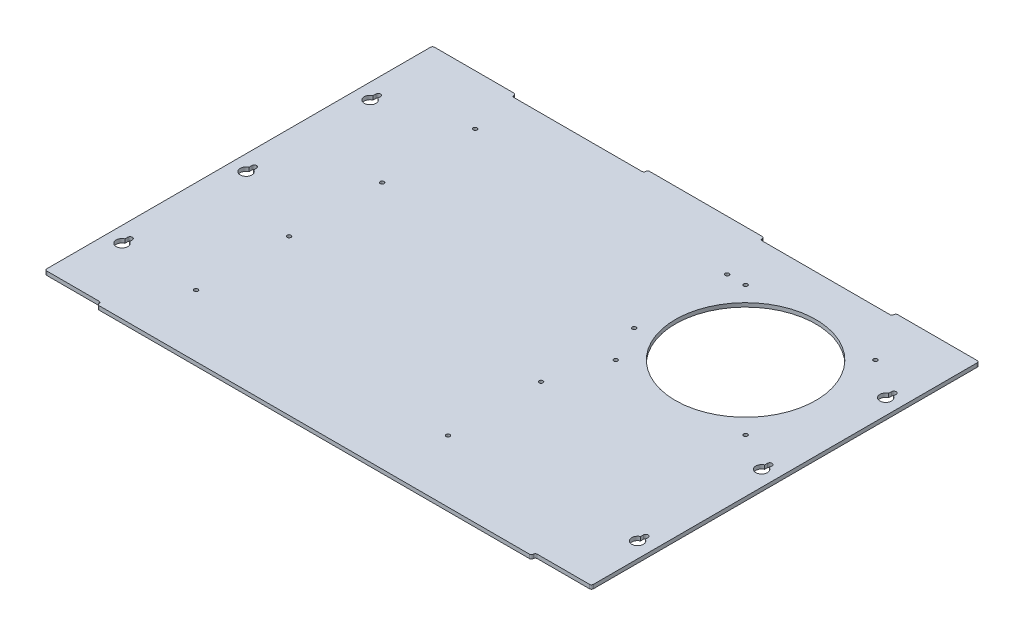
SolidWorks part; units mm, degrees
ref_plane "Front Plane" through (0, 0, 0) normal (0, 0, 1) x (1, 0, 0)
ref_plane "Top Plane" through (0, 0, 0) normal (0, 1, 0) x (1, 0, 0)
ref_plane "Right Plane" through (0, 0, 0) normal (1, 0, 0) x (0, 0, -1)
sketch "Sketch1" plane through (0, 0, 0) normal (0, 1, 0) x (1, 0, 0)
  line L0 (401.6375, 0) -> (447.675, 0)
  line L1 (0, 0) -> (46.0375, 0)
  line L2 (0, 0) -> (0, 317.5)
  line L3 (0, 317.5) -> (447.675, 317.5)
  line L4 (447.675, 0) -> (447.675, 317.5)
  line L6 (46.0375, 0) -> (46.0375, -3.175)
  line L7 (46.0375, -3.175) -> (401.6375, -3.175)
  line L8 (401.6375, 0) -> (401.6375, -3.175)
  point P9 (223.8375, -3.175)
  point P10 (223.8375, 317.5)
  dimension "D1" = 447.675
  dimension "D2" = 317.5
  dimension "D3" = 355.6
  dimension "D4" = 3.175
extrude "Boss-Extrude1" add sketch "Sketch1" along normal blind 3.175
sketch "Sketch3" plane through (0, 3.175, 0) normal (0, 1, 0) x (1, 0, 0)
  line L0 (447.675, 317.5) -> (0, 317.5) construction
  line L1 (68.2625, 317.5) -> (176.2125, 317.5)
  line L2 (68.2625, 317.5) -> (68.2625, 314.325)
  line L3 (68.2625, 314.325) -> (176.2125, 314.325)
  line L4 (176.2125, 317.5) -> (176.2125, 314.325)
  line L5 (176.2125, 314.325) -> (271.4625, 314.325) construction
  line L6 (271.4625, 317.5) -> (379.4125, 317.5)
  line L7 (271.4625, 317.5) -> (271.4625, 314.325)
  line L8 (271.4625, 314.325) -> (379.4125, 314.325)
  line L9 (379.4125, 317.5) -> (379.4125, 314.325)
  point P10 (223.8375, 317.5)
  point P11 (223.8375, 314.325)
  dimension "D1" = 3.175
  dimension "D2" = 107.95
  dimension "D3" = 95.25
extrude "Cut-Extrude2" cut sketch "Sketch3" against normal through all
fillet "Fillet1" radius 1.5875 16 edges at (379.4125, 1.5875, -317.5) (271.4625, 1.5875, -317.5) (176.2125, 1.5875, -317.5) (68.2625, 1.5875, -317.5) (379.4125, 1.5875, -314.325) (271.4625, 1.5875, -314.325) (176.2125, 1.5875, -314.325) (68.2625, 1.5875, -314.325) (447.675, 1.5875, -317.5) (447.675, 1.5875, 0) (0, 1.5875, 0) (0, 1.5875, -317.5) (401.6375, 1.5875, 3.175) (401.6375, 1.5875, 0) (46.0375, 1.5875, 3.175) (46.0375, 1.5875, 0)
sketch "Sketch2" plane through (0, 3.175, 0) normal (0, 1, 0) x (1, 0, 0)
  line L0 (0, 315.9125) -> (0, 1.5875) construction
  line L3 (66.675, 317.5) -> (1.5875, 317.5) construction
  line L7 (12.7, 253.6825) -> (12.7, 260.35) construction
  line L8 (10.795, 258.0474) -> (10.795, 260.35)
  line L9 (14.605, 258.0474) -> (14.605, 260.35)
  arc A3 (10.795, 258.0474) -> (14.605, 258.0474) centre (12.7, 253.6825) ccw
  arc A4 (14.605, 260.35) -> (10.795, 260.35) centre (12.7, 260.35) ccw
  point P17 (14.6321, 297.909)
  dimension "D2" = 57.15
  dimension "D6" = 9.525
  dimension "D1" = 12.7
  dimension "D5" = 3.81
  dimension "D7" = 6.6675
extrude "Cut-Extrude1" cut sketch "Sketch2" against normal through all
pattern_linear "LPattern1" count 3 spacing 101.6 along (0, 0, 1) of "Cut-Extrude1"
ref_plane "Plane1" through (223.8375, 0, 0) normal (-1, 0, 0) x (0, 0, 1)
mirror "Mirror1" about plane through (223.8375, 0, 0) normal (-1, 0, 0) of "LPattern1"
sketch "Sketch4" plane through (0, 3.175, 0) normal (0, 1, 0) x (1, 0, 0)
  line L0 (403.225, 0) -> (446.0875, 0) construction
  line L1 (25.4, 314.325) -> (422.275, 314.325) construction
  line L2 (25.4, 314.325) -> (25.4, 0) construction
  line L3 (25.4, 0) -> (422.275, 0) construction
  line L4 (422.275, 314.325) -> (422.275, 0) construction
  line L5 (69.85, 314.325) -> (174.625, 314.325) construction
  line L6 (0, 315.9125) -> (0, 1.5875) construction
  line L7 (447.675, 1.5875) -> (447.675, 315.9125) construction
  line L8 (282.575, 0) -> (282.575, 314.325) construction
  line L9 (76.2, 314.325) -> (76.2, 0) construction
  circle A0 centre (282.575, 276.225) radius 1.5875
  circle A1 centre (76.2, 276.225) radius 1.5875
  dimension "D4" = 3.175
  dimension "D7" = 3.175
  dimension "D1" = 25.4
  dimension "D2" = 25.4
  dimension "D3" = 257.175
  dimension "D5" = 38.1
  dimension "D6" = 50.8
extrude "Cut-Extrude3" cut sketch "Sketch4" against normal through all
pattern_linear "LPattern2" count 4 spacing 76.2 along (0, 0, 1) of "Cut-Extrude3"
sketch "Sketch5" plane through (0, 3.175, 0) normal (0, 1, 0) x (1, 0, 0)
  line L0 (273.05, 314.325) -> (377.825, 314.325) construction
  line L1 (282.575, 314.325) -> (419.1, 314.325) construction
  line L2 (282.575, 314.325) -> (282.575, 0) construction
  line L3 (282.575, 0) -> (419.1, 0) construction
  line L4 (419.1, 314.325) -> (419.1, 0) construction
  line L5 (403.225, 0) -> (446.0875, 0) construction
  line L6 (447.675, 1.5875) -> (447.675, 315.9125) construction
  line L7 (297.6562, 276.225) -> (404.0188, 276.225) construction
  line L8 (290.8375, 283.0437) -> (410.8375, 283.0437) construction
  line L9 (290.8375, 283.0437) -> (290.8375, 163.0437) construction
  line L10 (290.8375, 163.0437) -> (410.8375, 163.0437) construction
  line L11 (410.8375, 283.0437) -> (410.8375, 163.0437) construction
  line L12 (404.0188, 276.225) -> (404.0187, 169.8625) construction
  line L13 (297.6562, 276.225) -> (297.6562, 169.8625) construction
  line L14 (297.6562, 169.8625) -> (404.0187, 169.8625) construction
  circle A0 centre (297.6562, 276.225) radius 1.5875
  circle A1 centre (404.0188, 276.225) radius 1.5875
  circle A2 centre (282.575, 276.225) radius 1.5875 construction
  circle A3 centre (282.575, 276.225) radius 1.5875 construction
  circle A4 centre (404.0187, 169.8625) radius 1.5875
  circle A5 centre (297.6562, 169.8625) radius 1.5875
  circle A6 centre (350.8375, 223.0437) radius 57.5
  point P11 (350.8375, 314.325)
  point P18 (350.8375, 283.0438)
  point P27 (350.8375, 276.225)
  point P28 (404.0188, 223.0437)
  point P29 (410.8375, 223.0437)
  dimension "D3" = 3.175
  dimension "D8" = 115
  dimension "D1" = 28.575
  dimension "D2" = 120
  dimension "D4" = 106.3625
  dimension "D5" = 106.3625
extrude "Cut-Extrude4" cut sketch "Sketch5" against normal through all
